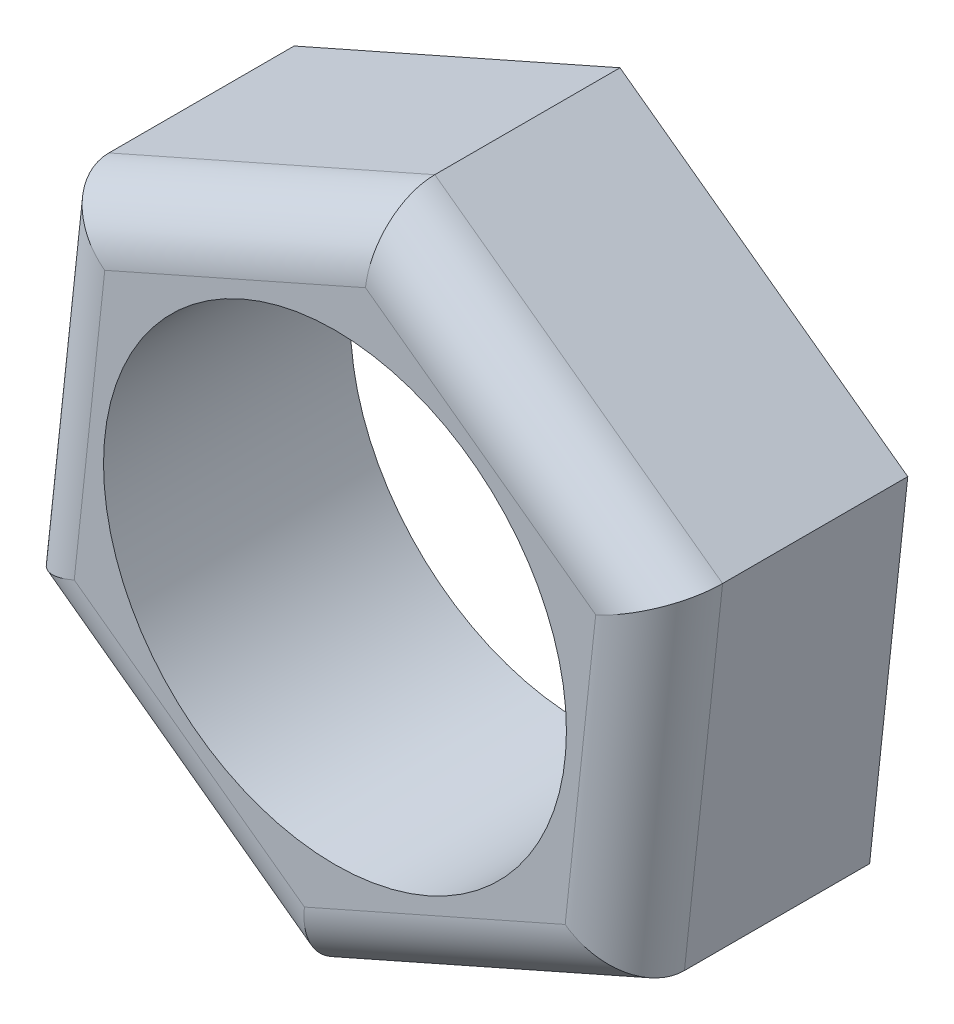
SolidWorks part; units mm, degrees
ref_plane "Front Plane" through (0, 0, 0) normal (0, 0, 1) x (1, 0, 0)
ref_plane "Top Plane" through (0, 0, 0) normal (0, 1, 0) x (1, 0, 0)
ref_plane "Right Plane" through (0, 0, 0) normal (1, 0, 0) x (0, 0, -1)
sketch "Sketch1" plane through (0, 0, 0) normal (0, 0, 1) x (1, 0, 0)
  line L1 (6.706, 2.9653) -> (0.7849, 7.2902)
  line L2 (0.7849, 7.2902) -> (-5.921, 4.3249)
  line L3 (-5.921, 4.3249) -> (-6.706, -2.9653)
  line L4 (-6.706, -2.9653) -> (-0.7849, -7.2902)
  line L5 (-0.7849, -7.2902) -> (5.921, -4.3249)
  line L6 (5.921, -4.3249) -> (6.706, 2.9653)
  circle A0 centre (0, 0) radius 4.7625
  circle A1 centre (0, 0) radius 6.35 construction
  dimension "D1" = 9.525
  dimension "D2" = 12.7
extrude "Boss-Extrude1" add sketch "Sketch1" along normal blind 5.08
fillet "Fillet1" radius 1.27 6 edges at (-3.7455, -5.1278, 5.08) (2.568, -5.8076, 5.08) (6.3135, -0.6798, 5.08) (3.7455, 5.1278, 5.08) (-6.3135, 0.6798, 5.08) (-2.568, 5.8076, 5.08)
ref_axis "Axis1" through (0, 0, 5.08) along (0, 0, -1)
